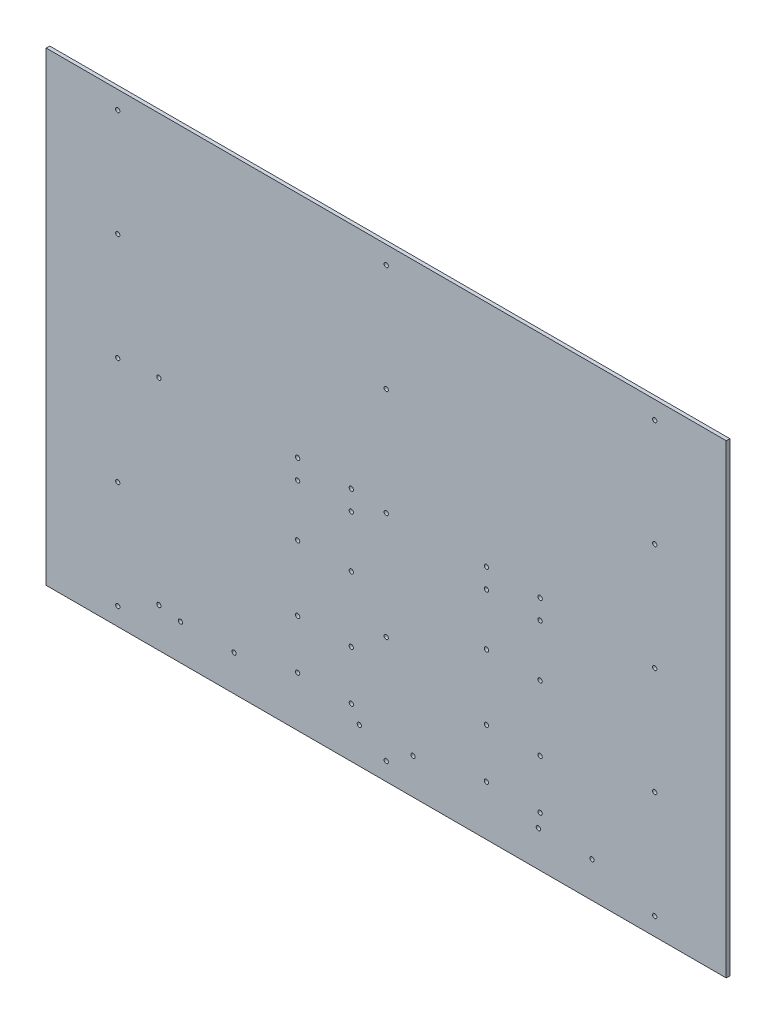
SolidWorks part; units mm, degrees
ref_plane "Płaszczyzna przednia" through (0, 0, 0) normal (0, 0, 1) x (1, 0, 0)
ref_plane "Płaszczyzna górna" through (0, 0, 0) normal (0, 1, 0) x (1, 0, 0)
ref_plane "Płaszczyzna prawa" through (0, 0, 0) normal (1, 0, 0) x (0, 0, -1)
sketch "Szkic1" plane through (0, 0, 0) normal (0, 0, 1) x (1, 0, 0)
  line L1 (-950, -650) -> (950, -650)
  line L2 (-950, -650) -> (-950, 650)
  line L3 (-950, 650) -> (950, 650)
  line L4 (950, -650) -> (950, 650)
  line L5 (-950, -650) -> (950, 650) construction
  line L6 (-950, 650) -> (950, -650) construction
  point P0 (0, 0)
  dimension "D1" = 1900
  dimension "D2" = 1300
extrude "Dodanie-wyciągnięcie1" add sketch "Szkic1" along normal blind 10
hole_wizard "Otwór pod śrubę M101" positions "Szkic2" profile "Szkic3" hole size "M10" standard "Ansi Metric" end condition through all
sketch "Szkic2" plane through (0, 0, 10) normal (0, 0, 1) x (1, 0, 0)
  line L0 (-950, 650) -> (-950, -650) construction
  line L2 (-950, -650) -> (950, -650) construction
  point P0 (-750, -600)
  dimension "D1" = 200
  dimension "D2" = 50
sketch "Szkic3" plane through (-750, -600, 10) normal (1, 0, 0) x (0, -1, 0)
  line L0 (0, 0) -> (0, 10)
  line L1 (0, 10) -> (6, 10)
  line L2 (6, 10) -> (6, 0)
  line L5 (6, 0) -> (0, 0)
  line L11 (0, -6.35) -> (0, 107.95) construction
  dimension "Średnica otworu na wylot" = 12
  dimension "Głębokość otworu na wylot" = 10
pattern_linear "Szyk liniowy1" count 5 spacing 300 along (0, 1, 0) count 3 spacing 750 along (1, 0, 0) of "Otwór pod śrubę M101"
hole_wizard "Otwór pod śrubę M103" positions "Szkic6" profile "Szkic7" hole size "M10" standard "Ansi Metric" end condition through all
sketch "Szkic6" plane through (0, 0, 10) normal (0, 0, 1) x (1, 0, 0)
  line L0 (-950, -650) -> (950, -650) construction
  circle A0 centre (0, -600) radius 6 construction
  point P0 (-75, -550)
  point P2 (75, -550)
  dimension "D1" = 100
  dimension "D2" = 100
  dimension "D3" = 150
  dimension "D4" = 75
sketch "Szkic7" plane through (-75, -550, 10) normal (1, 0, 0) x (0, -1, 0)
  line L0 (0, 0) -> (0, 10)
  line L1 (0, 10) -> (6, 10)
  line L2 (6, 10) -> (6, 0)
  line L5 (6, 0) -> (0, 0)
  line L11 (0, -6.35) -> (0, 107.95) construction
  dimension "Średnica otworu na wylot" = 12
  dimension "Głębokość otworu na wylot" = 10
hole_wizard "Otwór pod śrubę M104" positions "Szkic8" profile "Szkic9" hole size "M10" standard "Ansi Metric" end condition through all
sketch "Szkic8" plane through (0, 0, 10) normal (0, 0, 1) x (1, 0, 0)
  line L0 (-950, -650) -> (950, -650) construction
  circle A0 centre (0, -600) radius 6 construction
  point P0 (-575, -550)
  point P2 (-425, -550)
  point P4 (425, -550)
  point P6 (575, -550)
  dimension "D7" = 575
  dimension "D8" = 575
  dimension "D1" = 100
  dimension "D2" = 100
  dimension "D3" = 100
  dimension "D4" = 100
  dimension "D5" = 150
  dimension "D6" = 150
sketch "Szkic9" plane through (-575, -550, 10) normal (1, 0, 0) x (0, -1, 0)
  line L0 (0, 0) -> (0, 10)
  line L1 (0, 10) -> (6, 10)
  line L2 (6, 10) -> (6, 0)
  line L5 (6, 0) -> (0, 0)
  line L11 (0, -6.35) -> (0, 107.95) construction
  dimension "Średnica otworu na wylot" = 12
  dimension "Głębokość otworu na wylot" = 10
hole_wizard "Otwór pod śrubę M105" positions "Szkic10" profile "Szkic11" hole size "M10" standard "Ansi Metric" end condition through all
sketch "Szkic10" plane through (0, 0, 10) normal (0, 0, 1) x (1, 0, 0)
  point P0 (-635, -540)
  point P3 (-635, 10)
sketch "Szkic11" plane through (-635, -540, 10) normal (1, 0, 0) x (0, -1, 0)
  line L0 (0, 0) -> (0, 10)
  line L1 (0, 10) -> (6, 10)
  line L2 (6, 10) -> (6, 0)
  line L5 (6, 0) -> (0, 0)
  line L11 (0, -6.35) -> (0, 107.95) construction
  dimension "Średnica otworu na wylot" = 12
  dimension "Głębokość otworu na wylot" = 10
hole_wizard "Otwór pod śrubę M106" positions "Szkic12" profile "Szkic13" hole size "M10" standard "Ansi Metric" end condition through all
sketch "Szkic12" plane through (0, 0, 10) normal (0, 0, 1) x (1, 0, 0)
  point P0 (-247.5, -510)
  point P3 (-97.5, -510)
  point P6 (-97.5, -372.5)
  point P9 (-247.5, -372.5)
  point P12 (-97.5, -190)
  point P15 (-247.5, -190)
  point P18 (-247.5, -45)
  point P21 (-97.5, -45)
  point P24 (-97.5, 10)
  point P27 (-247.5, 10)
  point P30 (280, 10)
  point P33 (430, 10)
  point P36 (430, -45)
  point P39 (280, -45)
  point P42 (280, -190)
  point P45 (430, -190)
  point P48 (280, -372.5)
  point P51 (430, -372.5)
  point P54 (430, -510)
  point P57 (280, -510)
sketch "Szkic13" plane through (-247.5, -510, 10) normal (1, 0, 0) x (0, -1, 0)
  line L0 (0, 0) -> (0, 10)
  line L1 (0, 10) -> (6, 10)
  line L2 (6, 10) -> (6, 0)
  line L5 (6, 0) -> (0, 0)
  line L11 (0, -6.35) -> (0, 107.95) construction
  dimension "Średnica otworu na wylot" = 12
  dimension "Głębokość otworu na wylot" = 10
